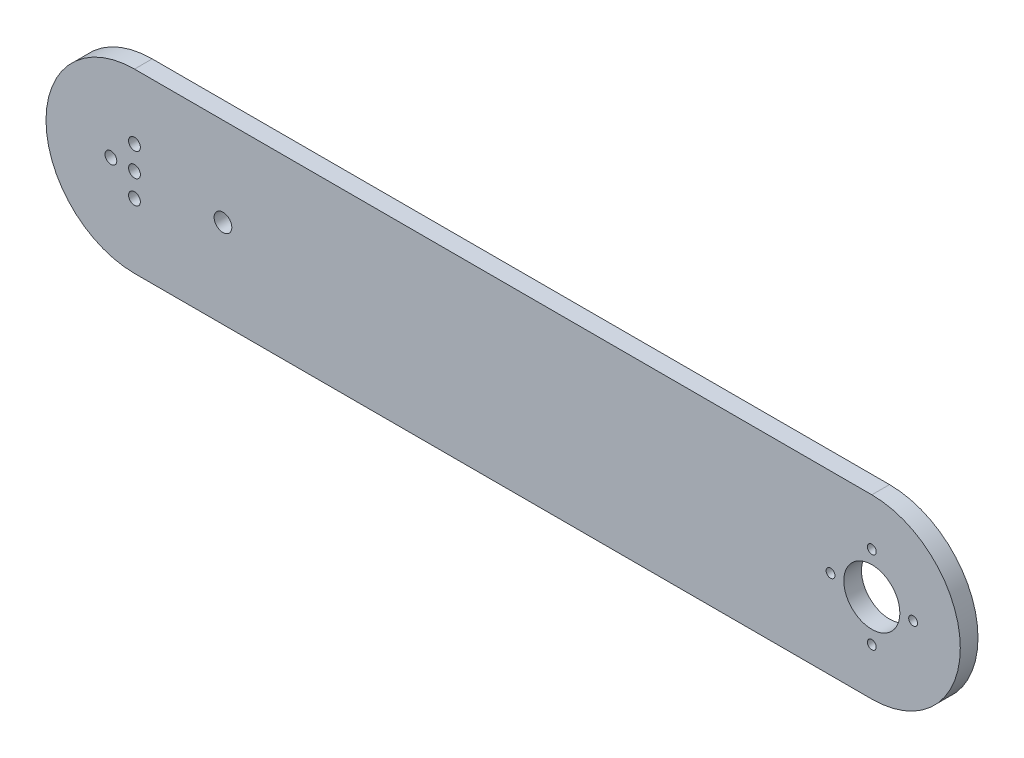
SolidWorks part; units mm, degrees
ref_plane "Alzado" through (0, 0, 0) normal (0, 0, 1) x (1, 0, 0)
ref_plane "Planta" through (0, 0, 0) normal (0, 1, 0) x (1, 0, 0)
ref_plane "Vista lateral" through (0, 0, 0) normal (1, 0, 0) x (0, 0, -1)
sketch "Croquis1" plane through (0, 0, 0) normal (0, 0, 1) x (1, 0, 0)
  line L0 (400, 60) -> (370, 60) construction
  line L1 (120, 0) -> (370, 0)
  line L3 (120, 60) -> (370, 60)
  arc A0 (370, 60) -> (370, 0) centre (370, 30) cw
  arc A3 (120, 60) -> (120, 0) centre (120, 30) ccw
  point P10 (0, 0)
  point P13 (0, 60)
  dimension "D4" = 30
  dimension "D1" = 30
  dimension "D2" = 250
  dimension "D3" = 30
extrude "Saliente-Extruir1" add sketch "Croquis1" along normal blind 6
sketch "Croquis2" plane through (0, 0, 6) normal (0, 0, 1) x (1, 0, 0)
  line L0 (370, 60) -> (370, 0) construction
  line L1 (120, 60) -> (120, 0) construction
  line L3 (43.4976, 30) -> (150, 30) construction
  line L4 (370, 60) -> (120, 60) construction
  circle A0 centre (370, 30) radius 9.5
  circle A3 centre (150, 30) radius 3
  arc A4 (120, 60) -> (120, 0) centre (120, 30) ccw construction
  circle A5 centre (120, 30) radius 2
  circle A7 centre (120, 22) radius 2
  circle A8 centre (120, 38) radius 2
  circle A9 centre (112, 30) radius 2
  dimension "D1" = 19
  dimension "D3" = 4
  dimension "D5" = 6
  dimension "D8" = 4
  dimension "D2" = 220
  dimension "D4" = 8
  dimension "D6" = 8
  dimension "D7" = 8
extrude "Cortar-Extruir4" cut sketch "Croquis2" against normal blind 220
sketch "Croquis7" plane through (0, 0, 6) normal (0, 0, 1) x (1, 0, 0)
  line L0 (370, 49.5) -> (370, 10.5) construction
  circle A1 centre (370, 16) radius 1.5
  circle A2 centre (384, 30) radius 1.5
  circle A3 centre (356, 30) radius 1.5
  circle A4 centre (370, 44) radius 1.5
  point P0 (370, 30)
  dimension "D1" = 3
  dimension "D5" = 39
  dimension "D6" = 14
  dimension "D7" = 14
  dimension "D8" = 14
  dimension "D9" = 14
extrude "Cortar-Extruir5" cut sketch "Croquis7" against normal blind 6
